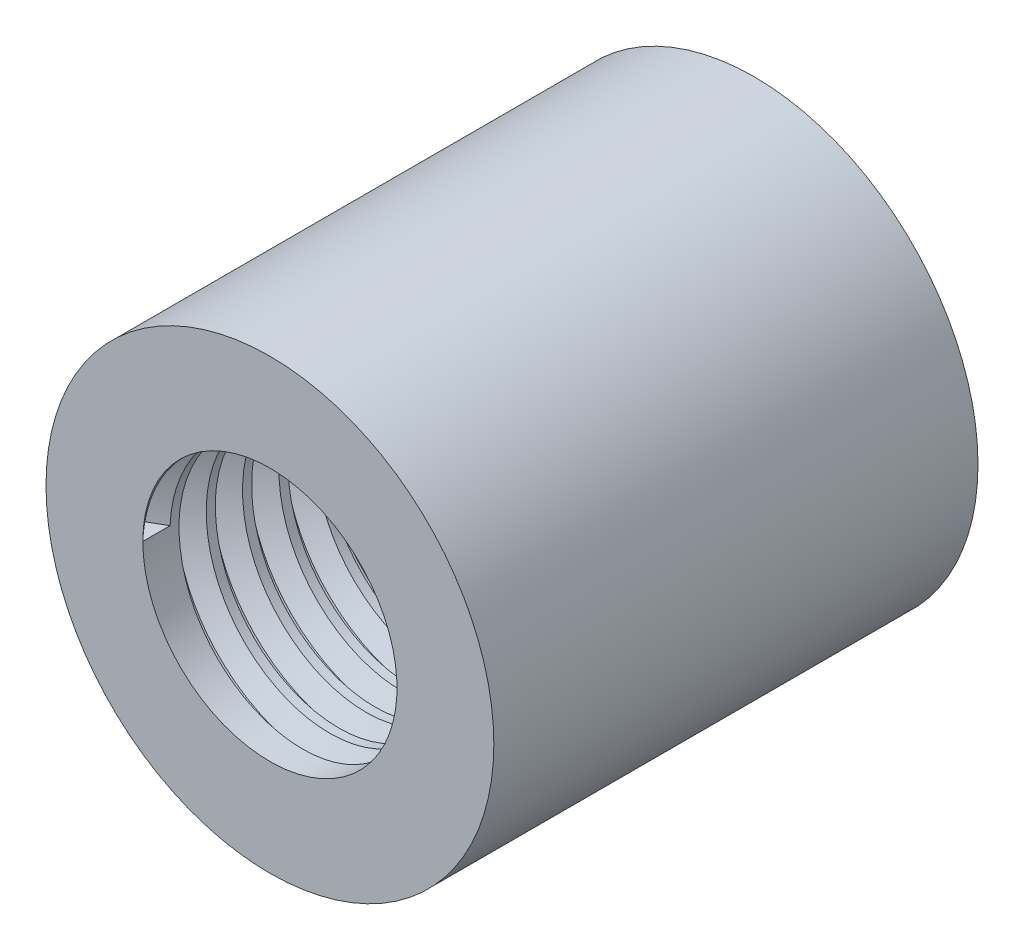
SolidWorks part; units mm, degrees
ref_plane "Front Plane" through (0, 0, 0) normal (0, 0, 1) x (1, 0, 0)
ref_plane "Top Plane" through (0, 0, 0) normal (0, 1, 0) x (1, 0, 0)
ref_plane "Right Plane" through (0, 0, 0) normal (1, 0, 0) x (0, 0, -1)
sketch "Sketch1" plane through (0, 0, 0) normal (0, 0, 1) x (1, 0, 0)
  circle A0 centre (0, 0) radius 9.25
  circle A1 centre (0, 0) radius 5.25
  dimension "D1" = 10.5
  dimension "D2" = 4
extrude "Boss-Extrude1" add sketch "Sketch1" along normal blind 20
sketch "Sketch4" plane through (0, 0, 0) normal (0, 0, -1) x (-1, 0, 0)
  circle A0 centre (0, 0) radius 6
  dimension "D1" = 12
extrude "Cut-Extrude1" cut sketch "Sketch4" against normal blind 12
thread "Thread1" pitch 1.5 method cut profile "Thread Profile2" start angle 0, offset 0, length 0, pitch 1.5, diameter 10.5
ref_plane "Plane2" through (-5.25, 0, 20) normal (0, -1, 0) x (-1, 0, 0)
sketch "Thread Profile2" plane through (-5.25, 0, 20) normal (0, -1, 0) x (-1, 0, 0)
  line L0 (0, 0) -> (0, 1.5) construction
  line L1 (0, 0) -> (0.8119, 0.4687)
  line L2 (0.8119, 0.4687) -> (0.8119, 0.6562)
  line L3 (0.8119, 0.6562) -> (0, 1.125)
  line L4 (0.8119, 0.5625) -> (0, 0.5625) construction
  line L11 (0, 0) -> (0, 1.125)
  point P2 (0, 0)
  dimension "Pitch" = 1.5
  dimension "Profile_Angle" = 60
  dimension "Profile_Land" = 0.1875
  dimension "Profile_Height" = 0.8119
sketch "Sketch11" plane through (0, 0, 0) normal (0, 1, 0) x (1, 0, 0)
  line L0 (9.25, 0) -> (-9.25, 0) construction
  circle A0 centre (0, -6) radius 4
  dimension "D1" = 8
  dimension "D2" = 6
extrude "Cut-Extrude2" cut sketch "Sketch11" against normal blind 12
